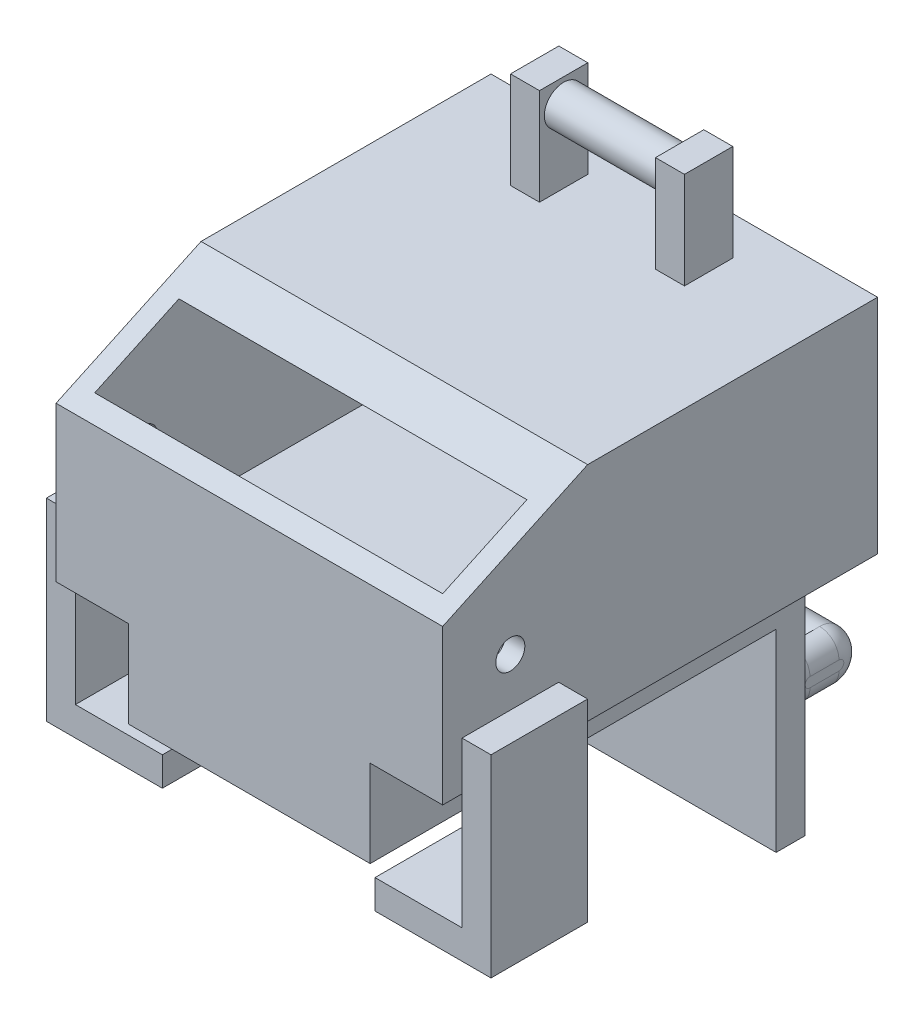
SolidWorks part; units mm, degrees
ref_plane "正面" through (0, 0, 0) normal (0, 0, 1) x (1, 0, 0)
ref_plane "平面" through (0, 0, 0) normal (0, 1, 0) x (1, 0, 0)
ref_plane "右側面" through (0, 0, 0) normal (1, 0, 0) x (0, 0, -1)
sketch "ｽｹｯﾁ1" plane through (0, 0, 0) normal (0, 1, 0) x (1, 0, 0)
  line L1 (0, 0) -> (25, 0)
  line L2 (0, 0) -> (0, 42)
  line L3 (0, 42) -> (25, 42)
  line L4 (25, 0) -> (25, 42)
  dimension "D1" = 25
  dimension "D2" = 42
extrude "ﾎﾞｽ - 押し出し1" add sketch "ｽｹｯﾁ1" along normal blind 9
sketch "ｽｹｯﾁ2" plane through (0, 0, -42) normal (0, 0, -1) x (-1, 0, 0)
  line L1 (-25, 9) -> (0, 9)
  line L2 (-25, 9) -> (-25, -20)
  line L3 (-25, -20) -> (0, -20)
  line L4 (0, 9) -> (0, -20)
  dimension "D1" = 29
extrude "ﾎﾞｽ - 押し出し2" add sketch "ｽｹｯﾁ2" along normal blind 3
sketch "ｽｹｯﾁ3" plane through (0, 9, 0) normal (0, 1, 0) x (1, 0, 0)
  line L1 (-7.5, 0) -> (32.5, 0)
  line L2 (-7.5, 0) -> (-7.5, 45)
  line L3 (-7.5, 45) -> (32.5, 45)
  line L4 (32.5, 0) -> (32.5, 45)
  line L5 (0, 0) -> (25, 0) construction
  line L6 (0, 45) -> (25, 45) construction
  line L7 (0, 45) -> (0, 0) construction
  dimension "D1" = 40
  dimension "D2" = 7.5
extrude "ﾎﾞｽ - 押し出し3" add sketch "ｽｹｯﾁ3" along normal blind 23
sketch "ｽｹｯﾁ4" plane through (0, 0, -45) normal (0, 0, -1) x (-1, 0, 0)
  line L0 (-32.5, 32) -> (7.5, 32) construction
  line L1 (5.5, 30) -> (-30.5, 30)
  line L2 (5.5, 30) -> (5.5, 11)
  line L3 (5.5, 11) -> (-30.5, 11)
  line L4 (-30.5, 30) -> (-30.5, 11)
  line L5 (7.5, 32) -> (7.5, 9) construction
  line L6 (-32.5, 32) -> (-32.5, 9) construction
  line L7 (0, 9) -> (7.5, 9) construction
  dimension "D1" = 2
  dimension "D2" = 2
  dimension "D3" = 2
  dimension "D4" = 2
extrude "ｶｯﾄ - 押し出し1" cut sketch "ｽｹｯﾁ4" against normal blind 43
sketch "ｽｹｯﾁ6" plane through (32.5, 0, 0) normal (1, 0, 0) x (0, 0, -1)
  line L0 (42, 0) -> (42, -20) construction
  line L1 (2, -6) -> (12, -6)
  line L2 (2, -6) -> (2, 14)
  line L3 (2, 14) -> (12, 14)
  line L4 (12, -6) -> (12, 14)
  line L5 (0, 9) -> (45, 9) construction
  dimension "D1" = 30
  dimension "D2" = 20
  dimension "D3" = 10
  dimension "D4" = 15
extrude "ﾎﾞｽ - 押し出し4" add sketch "ｽｹｯﾁ6" along normal blind 3
sketch "ｽｹｯﾁ7" plane through (0, -6, 0) normal (0, -1, 0) x (1, 0, 0)
  line L0 (35.5, -2) -> (32.5, -2) construction
  line L1 (32.5, -12) -> (23.5, -12)
  line L2 (32.5, -12) -> (32.5, -2)
  line L3 (32.5, -2) -> (23.5, -2)
  line L4 (23.5, -12) -> (23.5, -2)
  dimension "D1" = 9
extrude "ﾎﾞｽ - 押し出し5" add sketch "ｽｹｯﾁ7" against normal blind 3
ref_plane "平面1" through (12.5, 0, 0) normal (1, 0, 0) x (0, 0, -1)
mirror "ﾐﾗｰ1" about plane through (12.5, 0, 0) normal (1, 0, 0) of "ﾎﾞｽ - 押し出し4", "ﾎﾞｽ - 押し出し5"
sketch "ｽｹｯﾁ8" plane through (0, 32, 0) normal (0, 1, 0) x (1, 0, 0)
  line L0 (12.5, -15.95) -> (12.5, 15.95) construction
  line L1 (3.5, 41.0176) -> (6.5, 41.0176)
  line L2 (3.5, 41.0176) -> (3.5, 36.0176)
  line L3 (3.5, 36.0176) -> (6.5, 36.0176)
  line L4 (6.5, 41.0176) -> (6.5, 36.0176)
  line L5 (21.5, 36.0176) -> (18.5, 36.0176)
  line L6 (18.5, 41.0176) -> (18.5, 36.0176)
  line L7 (21.5, 41.0176) -> (18.5, 41.0176)
  line L8 (21.5, 41.0176) -> (21.5, 36.0176)
  dimension "D1" = 5
  dimension "D2" = 3
  dimension "D3" = 12
extrude "ﾎﾞｽ - 押し出し6" add sketch "ｽｹｯﾁ8" along normal blind 10
sketch "ｽｹｯﾁ9" plane through (6.5, 0, 0) normal (1, 0, 0) x (0, 0, -1)
  line L0 (36.0176, 42) -> (36.0176, 32) construction
  line L1 (36.0176, 42) -> (41.0176, 42) construction
  circle A0 centre (38.5176, 39.5) radius 2
  dimension "D1" = 4
  dimension "D2" = 2.5
  dimension "D3" = 2.5
extrude "ﾎﾞｽ - 押し出し7" add sketch "ｽｹｯﾁ9" along normal up to next
sketch "ｽｹｯﾁ10" plane through (-7.5, 0, 0) normal (-1, 0, 0) x (0, 0, 1)
  line L0 (-2, 9) -> (0, 9) construction
  line L1 (0, 32) -> (0, 9) construction
  circle A0 centre (-7, 19) radius 1.5
  dimension "D1" = 3
  dimension "D2" = 10
  dimension "D3" = 7
extrude "ｶｯﾄ - 押し出し2" cut sketch "ｽｹｯﾁ10" against normal through all
sketch "ｽｹｯﾁ11" plane through (0, 0, -45) normal (0, 0, -1) x (-1, 0, 0)
  line L1 (-25, -20) -> (0, -20) construction
  line L2 (-12.5, 15.95) -> (-12.5, -15.95) construction
  circle A0 centre (-12.5, -10) radius 2.5
  dimension "D1" = 5
  dimension "D2" = 10
extrude "ﾎﾞｽ - 押し出し8" add sketch "ｽｹｯﾁ11" along normal blind 7
sketch "ｽｹｯﾁ12" plane through (12.5, 0, 0) normal (1, 0, 0) x (0, 0, -1)
  line L0 (45, -12.5) -> (45, -7.5) construction
  line L2 (45, -12.5) -> (52, -12.5) construction
  circle A0 centre (52, -10) radius 2.5
  dimension "D1" = 5
  dimension "D2" = 7
  dimension "D3" = 2.5
extrude "ﾎﾞｽ - 押し出し9" add sketch "ｽｹｯﾁ12" along normal blind 7
sketch "ｽｹｯﾁ13" plane through (19.5, 0, 0) normal (1, 0, 0) x (0, 0, -1)
  line L0 (52, -10) -> (49, -10) construction
  line L1 (52, -12.5) -> (49, -12.5)
  line L2 (52, -7.5) -> (49, -7.5)
  arc A0 (52, -12.5) -> (52, -7.5) centre (52, -10) ccw
  arc A1 (49, -7.5) -> (49, -12.5) centre (49, -10) ccw
  circle A2 centre (52, -10) radius 2.5 construction
  point P2 (50.5, -10)
  dimension "D1" = 2.5
  dimension "D2" = 3
extrude "ﾎﾞｽ - 押し出し10" add sketch "ｽｹｯﾁ13" along normal blind 2
fillet "ﾌｨﾚｯﾄ1" radius 2 4 edges at (21.5, -12.5, -50.5) (21.5, -10, -46.5) (21.5, -7.5, -50.5) (21.5, -10, -54.5)
mirror "ﾐﾗｰ2" about plane through (12.5, 0, 0) normal (1, 0, 0) of "ﾌｨﾚｯﾄ1", "ﾎﾞｽ - 押し出し10", "ﾎﾞｽ - 押し出し9"
sketch "ｽｹｯﾁ14" plane through (-7.5, 0, 0) normal (-1, 0, 0) x (0, 0, 1)
  line L0 (-15, 32) -> (0, 25)
  line L1 (-45, 32) -> (0, 32) construction
  line L2 (0, 32) -> (0, 9) construction
  line L3 (0, 25) -> (0, 32)
  line L4 (0, 32) -> (-15, 32)
  dimension "D1" = 15
  dimension "D2" = 7
extrude "ｶｯﾄ - 押し出し3" cut sketch "ｽｹｯﾁ14" against normal through all
